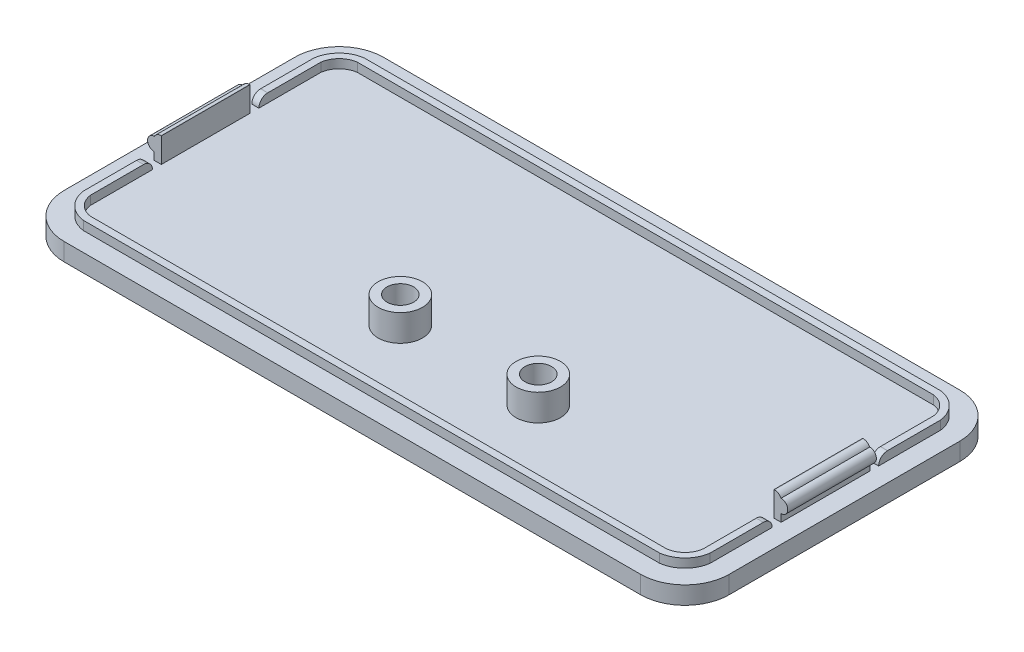
SolidWorks part; units mm, degrees
ref_plane "前视基准面" through (0, 0, 0) normal (0, 0, 1) x (1, 0, 0)
ref_plane "上视基准面" through (0, 0, 0) normal (0, 1, 0) x (1, 0, 0)
ref_plane "右视基准面" through (0, 0, 0) normal (1, 0, 0) x (0, 0, -1)
sketch "zero" plane through (0, 0, 0) normal (0, 1, 0) x (1, 0, 0)
  line L1 (-29.5, 15) -> (29.5, 15)
  line L2 (-32.5, 12) -> (-32.5, -12)
  line L3 (-29.5, -15) -> (29.5, -15)
  line L4 (32.5, 12) -> (32.5, -12)
  line L5 (-32.5, 15) -> (32.5, -15) construction
  line L6 (-32.5, -15) -> (32.5, 15) construction
  line L7 (-25.7, -15) -> (-14.5, -15)
  line L8 (-25.7, -15) -> (-25.7, -9.6569)
  line L9 (-25.7, -9.6569) -> (-14.5, -9.6569)
  line L10 (-14.5, -15) -> (-14.5, -9.6569)
  line L11 (5.2, -15) -> (12.7, -15)
  line L12 (5.2, -15) -> (5.2, -11)
  line L13 (5.2, -11) -> (12.7, -11)
  line L14 (12.7, -15) -> (12.7, -11)
  line L15 (17.8, -15) -> (25.3, -15)
  line L16 (17.8, -15) -> (17.8, -11)
  line L17 (17.8, -11) -> (25.3, -11)
  line L18 (25.3, -15) -> (25.3, -11)
  line L19 (-32.5, 7.7) -> (-19.5, 7.7)
  line L20 (-32.5, 7.7) -> (-32.5, -4.3)
  line L21 (-32.5, -4.3) -> (-19.5, -4.3)
  line L22 (-19.5, 7.7) -> (-19.5, -4.3)
  line L23 (-25.5, 14) -> (25.5, 14)
  line L24 (-25.5, 14) -> (-25.5, 8.8)
  line L25 (-25.5, 8.8) -> (25.5, 8.8)
  line L26 (25.5, 14) -> (25.5, 8.8)
  line L27 (-19.5, 7.2329) -> (-35.5, 7.2329)
  line L28 (-19.5, 7.2329) -> (-19.5, -3.7671)
  line L29 (-19.5, -3.7671) -> (-35.5, -3.7671)
  line L30 (-35.5, 7.2329) -> (-35.5, -3.7671)
  arc A0 (29.5, -15) -> (32.5, -12) centre (29.5, -12) ccw
  arc A1 (29.5, 15) -> (32.5, 12) centre (29.5, 12) cw
  arc A2 (-32.5, -12) -> (-29.5, -15) centre (-29.5, -12) ccw
  arc A3 (-29.5, 15) -> (-32.5, 12) centre (-29.5, 12) ccw
  circle A4 centre (-29, 11.4) radius 3
  circle A5 centre (-29, -11.5) radius 3
  circle A6 centre (29, 11.4) radius 3
  circle A7 centre (29, -11.5) radius 3
  circle A8 centre (-29, 11.4) radius 1.375
  circle A9 centre (-29, -11.5) radius 1.375
  circle A10 centre (29, -11.5) radius 1.375
  circle A11 centre (29, 11.4) radius 1.375
  point P0 (0, 0)
  dimension "D3" = 3
  dimension "D4" = 6
  dimension "D9" = 2.75
  dimension "D1" = 65
  dimension "D2" = 30
  dimension "D5" = 3.6
  dimension "D6" = 3.5
  dimension "D7" = 3.5
  dimension "D8" = 3.5
  dimension "D10" = 12
  dimension "D11" = 7.3
  dimension "D12" = 13
  dimension "D13" = 11.2
  dimension "D14" = 6.8
  dimension "D15" = 19.7
  dimension "D16" = 7.5
  dimension "D17" = 7.5
  dimension "D18" = 5.1
  dimension "D19" = 4
  dimension "D20" = 5.2
  dimension "D21" = 7
  dimension "D22" = 7
  dimension "D23" = 1
  dimension "D24" = 11
  dimension "D25" = 16
sketch "sugar" plane through (0, 0, 0) normal (0, 1, 0) x (1, 0, 0)
  line L1 (-29.5, 15) -> (29.5, 15)
  line L2 (-32.5, 12) -> (-32.5, -12)
  line L3 (-29.5, -15) -> (29.5, -15)
  line L4 (32.5, 12) -> (32.5, -12)
  line L5 (-32.5, 15) -> (32.5, -15) construction
  line L6 (-32.5, -15) -> (32.5, 15) construction
  line L7 (23.5, -11.5) -> (19.5, -11.5)
  line L8 (23.5, -11.5) -> (23.5, -13.9082)
  line L9 (23.5, -13.9082) -> (19.5, -13.9082)
  line L10 (19.5, -11.5) -> (19.5, -13.9082)
  line L11 (16, -11.0071) -> (8.5, -11.0071)
  line L12 (16, -11.0071) -> (16, -15)
  line L13 (16, -15) -> (8.5, -15)
  line L14 (8.5, -11.0071) -> (8.5, -15)
  line L15 (20.5, -13.9082) -> (22.5, -13.9082)
  line L16 (20.5, -13.9082) -> (20.5, -14.8173)
  line L17 (20.5, -14.8173) -> (22.5, -14.8173)
  line L18 (22.5, -13.9082) -> (22.5, -14.8173)
  arc A0 (29.5, 15) -> (32.5, 12) centre (29.5, 12) cw
  arc A1 (29.5, -15) -> (32.5, -12) centre (29.5, -12) ccw
  arc A2 (-32.5, -12) -> (-29.5, -15) centre (-29.5, -12) ccw
  arc A3 (-29.5, 15) -> (-32.5, 12) centre (-29.5, 12) ccw
  circle A4 centre (-29, 11.4) radius 3
  circle A5 centre (-29, 11.4) radius 1.375
  circle A6 centre (-29, -11.5) radius 3
  circle A7 centre (-29, -11.5) radius 1.375
  circle A8 centre (29, 11.4) radius 3
  circle A9 centre (29, 11.4) radius 1.375
  circle A10 centre (29, -11.5) radius 3
  circle A11 centre (29, -11.5) radius 1.375
  dimension "D3" = 3
  dimension "D1" = 65
  dimension "D2" = 30
  dimension "D4" = 9
  dimension "D5" = 4
  dimension "D6" = 3.5
  dimension "D7" = 7.5
  dimension "D8" = 2
  dimension "D9" = 1
sketch "case" plane through (0, 0, 0) normal (0, 1, 0) x (1, 0, 0)
  line L1 (-34.0422, 18) -> (30.9578, 18)
  line L2 (-39.0422, 13) -> (-39.0422, -13)
  line L3 (-34.0422, -18) -> (30.9578, -18)
  line L4 (35.9578, 13) -> (35.9578, -13)
  line L5 (-39.0422, 18) -> (35.9578, -18) construction
  line L6 (-39.0422, -18) -> (35.9578, 18) construction
  arc A0 (-39.0422, -13) -> (-34.0422, -18) centre (-34.0422, -13) ccw
  arc A1 (30.9578, -18) -> (35.9578, -13) centre (30.9578, -13) ccw
  arc A2 (30.9578, 18) -> (35.9578, 13) centre (30.9578, 13) cw
  arc A3 (-34.0422, 18) -> (-39.0422, 13) centre (-34.0422, 13) ccw
  point P0 (-1.5422, 0)
  point P3 (-1.5422, 0)
  dimension "D3" = 5
  dimension "D1" = 75
  dimension "D2" = 36
extrude "凸台-拉伸2" add sketch "case" along normal blind 2
sketch "草图2" plane through (0, 0, 0) normal (0, 1, 0) x (1, 0, 0)
  line L4 (-34.0422, -15.05) -> (30.9578, -15.05)
  line L5 (33.0078, -13) -> (33.0078, 13)
  line L6 (30.9578, 15.05) -> (-34.0422, 15.05)
  line L7 (-36.0922, 13) -> (-36.0922, -13)
  line L12 (33.8078, -13) -> (33.8078, 13)
  line L13 (30.9578, 15.85) -> (-34.0422, 15.85)
  line L14 (-36.8922, 13) -> (-36.8922, -13)
  line L15 (-34.0422, -15.85) -> (30.9578, -15.85)
  arc A4 (30.9578, -15.05) -> (33.0078, -13) centre (30.6303, -12.6725) ccw
  arc A5 (33.0078, 13) -> (30.9578, 15.05) centre (30.6303, 12.6725) ccw
  arc A6 (-34.0422, 15.05) -> (-36.0922, 13) centre (-33.7147, 12.6725) ccw
  arc A7 (-36.0922, -13) -> (-34.0422, -15.05) centre (-33.7147, -12.6725) ccw
  arc A12 (30.9578, -15.85) -> (33.8078, -13) centre (30.535, -12.5772) ccw
  arc A13 (33.8078, 13) -> (30.9578, 15.85) centre (30.535, 12.5772) ccw
  arc A14 (-34.0422, 15.85) -> (-36.8922, 13) centre (-33.6194, 12.5772) ccw
  arc A15 (-36.8922, -13) -> (-34.0422, -15.85) centre (-33.6194, -12.5772) ccw
ref_plane "基准面1" through (0, 2, 0) normal (0, 1, 0) x (1, 0, 0)
sketch "草图3" plane through (0, 2, 0) normal (0, 1, 0) x (1, 0, 0)
  line L4 (-34.0422, -15.05) -> (30.9578, -15.05)
  line L5 (33.0078, -13) -> (33.0078, 13)
  line L6 (30.9578, 15.05) -> (-34.0422, 15.05)
  line L7 (-36.0922, 13) -> (-36.0922, -13)
  line L8 (-34.0422, -15.05) -> (30.9578, -15.05)
  line L9 (33.0078, -13) -> (33.0078, 13)
  line L10 (30.9578, 15.05) -> (-34.0422, 15.05)
  line L11 (-36.0922, 13) -> (-36.0922, -13)
  line L12 (-36.8922, 13) -> (-36.8922, -13)
  line L13 (-34.0422, -15.85) -> (30.9578, -15.85)
  line L14 (33.8078, -13) -> (33.8078, 13)
  line L15 (30.9578, 15.85) -> (-34.0422, 15.85)
  line L16 (-36.8922, 13) -> (-36.8922, -13)
  line L17 (-34.0422, -15.85) -> (30.9578, -15.85)
  line L18 (33.8078, -13) -> (33.8078, 13)
  line L19 (30.9578, 15.85) -> (-34.0422, 15.85)
  arc A4 (30.9578, -15.05) -> (33.0078, -13) centre (30.6303, -12.6725) ccw
  arc A5 (33.0078, 13) -> (30.9578, 15.05) centre (30.6303, 12.6725) ccw
  arc A6 (-34.0422, 15.05) -> (-36.0922, 13) centre (-33.7147, 12.6725) ccw
  arc A7 (-36.0922, -13) -> (-34.0422, -15.05) centre (-33.7147, -12.6725) ccw
  arc A8 (30.9578, -15.05) -> (33.0078, -13) centre (30.6303, -12.6725) ccw
  arc A9 (33.0078, 13) -> (30.9578, 15.05) centre (30.6303, 12.6725) ccw
  arc A10 (-34.0422, 15.05) -> (-36.0922, 13) centre (-33.7147, 12.6725) ccw
  arc A11 (-36.0922, -13) -> (-34.0422, -15.05) centre (-33.7147, -12.6725) ccw
  arc A12 (-36.8922, -13) -> (-34.0422, -15.85) centre (-33.6194, -12.5772) ccw
  arc A13 (30.9578, -15.85) -> (33.8078, -13) centre (30.535, -12.5772) ccw
  arc A14 (33.8078, 13) -> (30.9578, 15.85) centre (30.535, 12.5772) ccw
  arc A15 (-34.0422, 15.85) -> (-36.8922, 13) centre (-33.6194, 12.5772) ccw
  arc A16 (-36.8922, -13) -> (-34.0422, -15.85) centre (-33.6194, -12.5772) ccw
  arc A17 (30.9578, -15.85) -> (33.8078, -13) centre (30.535, -12.5772) ccw
  arc A18 (33.8078, 13) -> (30.9578, 15.85) centre (30.535, 12.5772) ccw
  arc A19 (-34.0422, 15.85) -> (-36.8922, 13) centre (-33.6194, 12.5772) ccw
  dimension "D1" = 0
  dimension "D2" = 0
extrude "凸台-拉伸4" add sketch "草图3" along normal blind 1
ref_plane "基准面3" through (33.8078, 0, 0) normal (1, 0, 0) x (0, 0, -1)
sketch "草图7" plane through (0, 2, 0) normal (0, 1, 0) x (1, 0, 0)
  line L0 (-36.8922, 13) -> (-36.8922, -13) construction
  line L1 (-36.8922, 5) -> (-36.0922, 5)
  line L2 (-36.8922, 5) -> (-36.8922, -5)
  line L3 (-36.8922, -5) -> (-36.0922, -5)
  line L4 (-36.0922, 5) -> (-36.0922, -5)
  line L5 (-36.0922, 13) -> (-36.0922, -13) construction
  point P10 (-36.0922, 0)
  dimension "D1" = 5
  dimension "D2" = 10
extrude "凸台-拉伸8" add sketch "草图7" along normal blind 2.8
ref_plane "基准面5" through (0, 0, 5) normal (0, 0, 1) x (1, 0, 0)
sketch "草图8" plane through (0, 0, 5) normal (0, 0, 1) x (1, 0, 0)
  line L0 (-34.0422, 2) -> (-39.0422, 2) construction
  line L1 (-36.8922, 4.8) -> (-36.8922, 3) construction
  circle A0 centre (-36.8922, 3.6) radius 0.75
  dimension "D1" = 1.5
  dimension "D2" = 1.6
  dimension "D3" = 0
extrude "凸台-拉伸9" add sketch "草图8" against normal blind 10
fillet "圆角1" radius 0.85 1 edges at (-36.8922, 4.8, 0)
ref_plane "基准面7" through (-36.8922, 0, 0) normal (-1, 0, 0) x (0, 0, 1)
sketch "草图11" plane through (-36.8922, 0, 0) normal (-1, 0, 0) x (0, 0, 1)
  line L0 (-13, 2) -> (13, 2) construction
  line L1 (5, 3) -> (6, 3)
  line L2 (5, 3) -> (5, 2)
  line L3 (5, 2) -> (6, 2)
  line L4 (6, 3) -> (6, 2)
  line L6 (-5, 3) -> (-6, 3)
  line L7 (-5, 3) -> (-5, 2)
  line L8 (-5, 2) -> (-6, 2)
  line L9 (-6, 3) -> (-6, 2)
  dimension "D1" = 1
  dimension "D2" = 1
extrude "切除-拉伸1" cut sketch "草图11" against normal blind 1.2
fillet "圆角2" radius 1 2 edges at (-36.4922, 3, 6) (-36.4922, 3, -6)
ref_plane "基准面8" through (0, 0, 0) normal (0, -1, 0) x (-1, 0, 0)
sketch "草图13" plane through (0, 3, 0) normal (0, 1, 0) x (1, 0, 0)
  line L0 (33.0078, -13) -> (33.0078, 13) construction
  line L1 (33.0078, 5) -> (33.8078, 5)
  line L2 (33.0078, 5) -> (33.0078, -5)
  line L3 (33.0078, -5) -> (33.8078, -5)
  line L4 (33.8078, 5) -> (33.8078, -5)
  line L5 (33.8078, -13) -> (33.8078, 13) construction
  line L7 (35.9578, -13) -> (35.9578, 13) construction
  point P12 (35.9578, 0)
  point P13 (33.8078, 0)
  dimension "D1" = 10
sketch "Sketch3" plane through (0, 0, 0) normal (0, -1, 0) x (1, 0, 0)
  text T0 "<b>PeakPulse</b>" font "Century Gothic" height 10
extrude "Cut-Extrude1" cut sketch "Sketch3" against normal blind 1
extrude "凸台-拉伸10" add sketch "草图13" along normal blind 1.8
sketch "草图14" plane through (0, 0, 5) normal (0, 0, 1) x (1, 0, 0)
  line L0 (33.8078, 2) -> (30.9578, 2) construction
  line L1 (33.8078, 4.8) -> (33.8078, 3) construction
  circle A0 centre (33.8078, 3.6) radius 0.75
  dimension "D2" = 1.5
  dimension "D1" = 1.6
  dimension "D3" = 0
extrude "凸台-拉伸11" add sketch "草图14" against normal blind 10
fillet "圆角3" radius 0.85 1 edges at (33.8078, 4.8, 0)
sketch "草图15" plane through (0, 3, 0) normal (0, 1, 0) x (1, 0, 0)
  line L0 (33.8078, 5) -> (33.8078, 13) construction
  line L1 (33.0078, 5) -> (33.8078, 5)
  line L2 (33.0078, 5) -> (33.0078, 6)
  line L3 (33.0078, 6) -> (33.8078, 6)
  line L4 (33.8078, 5) -> (33.8078, 6)
  line L5 (33.8078, -13) -> (33.8078, -5) construction
  line L6 (33.0078, -5) -> (33.8078, -5)
  line L7 (33.0078, -5) -> (33.0078, -6)
  line L8 (33.0078, -6) -> (33.8078, -6)
  line L9 (33.8078, -5) -> (33.8078, -6)
  dimension "D1" = 1
  dimension "D2" = 1
extrude "切除-拉伸3" cut sketch "草图15" against normal blind 1
fillet "圆角4" radius 1 2 edges at (33.4078, 3, 6) (33.4078, 3, -6)
sketch "Sketch2" plane through (0, 2, 0) normal (0, 1, 0) x (1, 0, 0)
  line L0 (8.6467, -7.2235) -> (-6.9133, -7.2235)
  circle A0 centre (8.6467, -7.2235) radius 1.5
  circle A1 centre (-6.9133, -7.2235) radius 1.5
  circle A2 centre (-6.9133, -7.2235) radius 2.5
  circle A3 centre (8.6467, -7.2235) radius 2.5
extrude "Boss-Extrude1" add sketch "Sketch2" along normal blind 3 contours A2 A1 | A3 A0 region at (8.6467, 2, 4.7942) region at (-9.3426, 2, 7.2235)
